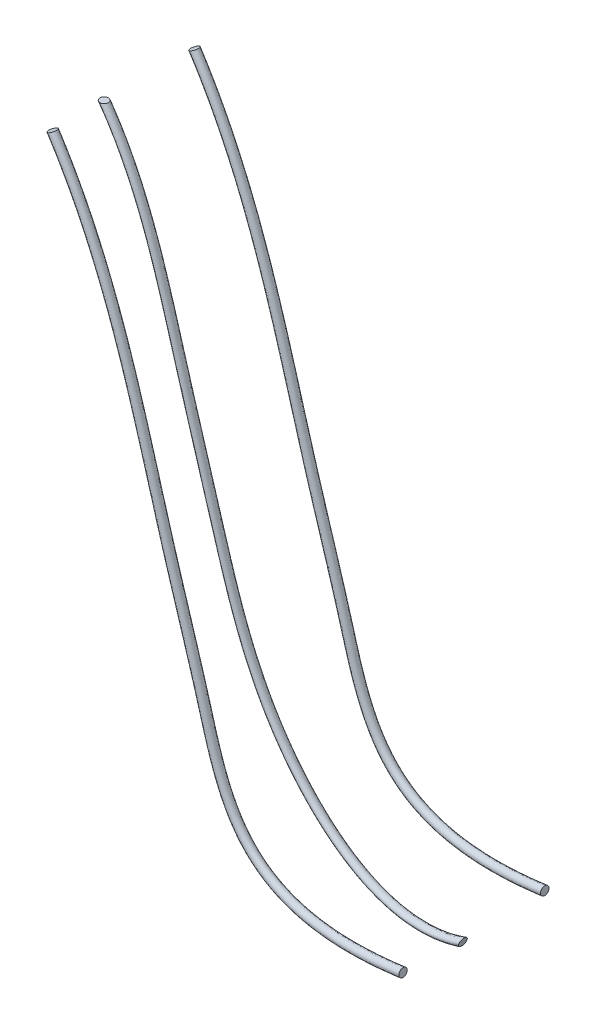
SolidWorks part; units mm, degrees
ref_plane "Front Plane" through (0, 0, 0) normal (0, 0, 1) x (1, 0, 0)
ref_plane "Top Plane" through (0, 0, 0) normal (0, 1, 0) x (1, 0, 0)
ref_plane "Right Plane" through (0, 0, 0) normal (1, 0, 0) x (0, 0, -1)
ref_plane "Plane1" through (0, 0, -10) normal (0, 0, 1) x (1, 0, 0)
sketch "Sketch2" plane through (0, 0, -10) normal (0, 0, 1) x (1, 0, 0)
  spline S0 degree 3 poles (20.7872, -47.5155) (-35.6803, -55.3641) (-44.5698, -13.8165) (-69.4332, 63.2552) (-81.2433, 114.6263) (-102.758, 147.9362) knots 0 0 0 0 0.351729 0.522411 1 1 1 1
ref_plane "Plane3" through (0, 0, -60) normal (0, 0, 1) x (1, 0, 0)
ref_plane "Plane4" through (20.7872, 0, 0) normal (1, 0, 0) x (0, 0, -1)
sketch "Sketch3" plane through (20.7872, 0, 0) normal (1, 0, 0) x (0, 0, -1)
  circle A0 centre (10, -47.5155) radius 1.5
  dimension "D1" = 3
sweep "Sweep1" add profiles "Sketch3" path "Sketch2"
sketch "Sketch4" plane through (0, 0, -60) normal (0, 0, 1) x (1, 0, 0)
  spline S0 degree 3 poles (1749.8735, 954.5358) (-18.1879, -183.6575) (-24.9729, -74.5631) (-118.3379, 214.8503) (-113.2508, 439.3197) (-2079.0983, -41.5495) knots -0.788183 -0.788183 -0.788183 -0.788183 0.351729 0.522411 2.966938 2.966938 2.966938 2.966938 only from (20.7872, -47.5155) to (-102.758, 147.9362) construction
  spline S1 degree 3 poles (20.7872, -47.5155) (-35.6803, -55.3641) (-44.5698, -13.8165) (-69.4332, 63.2552) (-81.2433, 114.6263) (-102.758, 147.9362) knots 0 0 0 0 0.351729 0.522411 1 1 1 1
sketch "Sketch5" plane through (20.7872, 0, 0) normal (1, 0, 0) x (0, 0, -1)
  circle A0 centre (60, -47.5155) radius 1.5
  dimension "D1" = 3
sweep "Sweep2" add profiles "Sketch5" path "Sketch4"
ref_plane "Plane5" through (0, 0, -35) normal (0, 0, 1) x (1, 0, 0)
sketch "Sketch6" plane through (0, 0, -35) normal (0, 0, 1) x (1, 0, 0)
  spline S0 degree 3 poles (16.9165, -52.6115) (-12.5214, -62.7175) (-52.4156, -25.9222) (-69.531, 31.0074) (-85.4551, 83.8164) (-96.1489, 122.2992) (-109.5919, 141.1975) knots 0 0 0 0 0.338631 0.527229 0.724053 1 1 1 1
ref_plane "Plane6" through (0, 141.1975, 0) normal (0, 1, 0) x (1, 0, 0)
sketch "Sketch7" plane through (0, 141.1975, 0) normal (0, 1, 0) x (1, 0, 0)
  circle A0 centre (-109.5919, 35) radius 1.5
  dimension "D1" = 3
sweep "Sweep3" add profiles "Sketch7" path "Sketch6"
